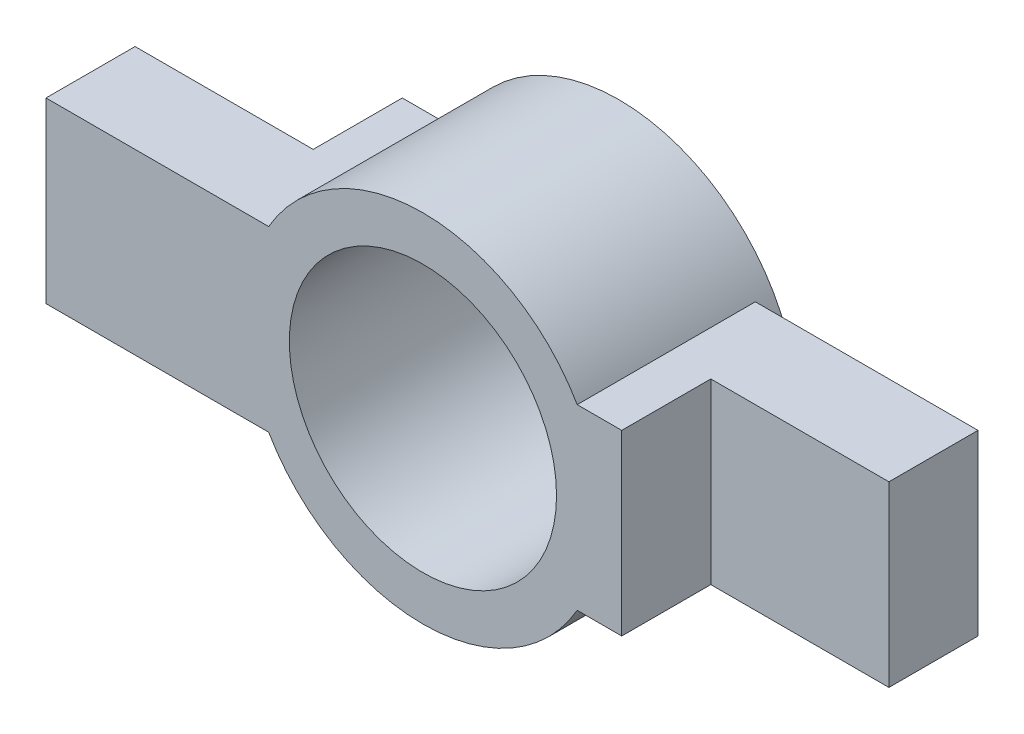
SolidWorks part; units mm, degrees
ref_plane "Alzado" through (0, 0, 0) normal (0, 0, 1) x (1, 0, 0)
ref_plane "Planta" through (0, 0, 0) normal (0, 1, 0) x (1, 0, 0)
ref_plane "Vista lateral" through (0, 0, 0) normal (1, 0, 0) x (0, 0, -1)
sketch "Croquis1" plane through (0, 0, 0) normal (0, 0, 1) x (1, 0, 0)
  circle A0 centre (0, 0) radius 20
  dimension "D1" = 40
extrude "Saliente-Extruir1" add sketch "Croquis1" along normal mid plane 22
sketch "Croquis6" plane through (0, 0, 11) normal (0, 0, 1) x (1, 0, 0)
  circle A0 centre (0, 0) radius 15
  dimension "D1" = 30
extrude "Cortar-Extruir1" cut sketch "Croquis6" against normal through all
sketch "Croquis7" plane through (0, 0, 11) normal (0, 0, 1) x (1, 0, 0)
  line L0 (0, 0) -> (-17.3205, 0) construction
  line L1 (-17.3205, 10) -> (-17.3205, -10)
  line L2 (-17.3205, 10) -> (-42.3205, 10)
  line L3 (-42.3205, 10) -> (-42.3205, -10)
  line L4 (-42.3205, -10) -> (-17.3205, -10)
  line L5 (0, 0) -> (0, 10) construction
  circle A0 centre (0, 0) radius 20 construction
  point P8 (-17.3205, 0)
  dimension "D1" = 20
  dimension "D2" = 25
extrude "Saliente-Extruir3" add sketch "Croquis7" against normal blind 20
sketch "Croquis8" plane through (0, 0, -9) normal (0, 0, -1) x (-1, 0, 0)
  line L0 (42.3205, 10) -> (22.3205, 10)
  line L1 (17.3205, 10) -> (42.3205, 10) construction
  line L2 (22.3205, 10) -> (22.3205, -10)
  line L3 (42.3205, -10) -> (17.3205, -10) construction
  line L4 (22.3205, -10) -> (42.3205, -10)
  line L5 (42.3205, -10) -> (42.3205, 10)
  line L6 (0, 0) -> (0, 10) construction
  line L7 (-22.3205, -10) -> (-42.3205, -10)
  line L8 (-22.3205, 10) -> (-22.3205, -10)
  line L9 (-42.3205, 10) -> (-22.3205, 10)
  line L10 (-42.3205, -10) -> (-42.3205, 10)
  dimension "D1" = 20
extrude "Cortar-Extruir2" cut sketch "Croquis8" against normal blind 10
mirror "Simetría1" about plane through (0, 0, 0) normal (1, 0, 0) of "Saliente-Extruir3"
sketch "Croquis9" plane through (0, 0, 11) normal (0, 0, 1) x (1, 0, 0)
  line L0 (42.3205, 10) -> (22.3205, 10)
  line L1 (17.3205, 10) -> (42.3205, 10) construction
  line L2 (22.3205, 10) -> (22.3205, -10)
  line L3 (42.3205, -10) -> (17.3205, -10) construction
  line L4 (22.3205, -10) -> (42.3205, -10)
  line L5 (42.3205, -10) -> (42.3205, 10)
  dimension "D1" = 20
extrude "Cortar-Extruir3" cut sketch "Croquis9" against normal blind 10
